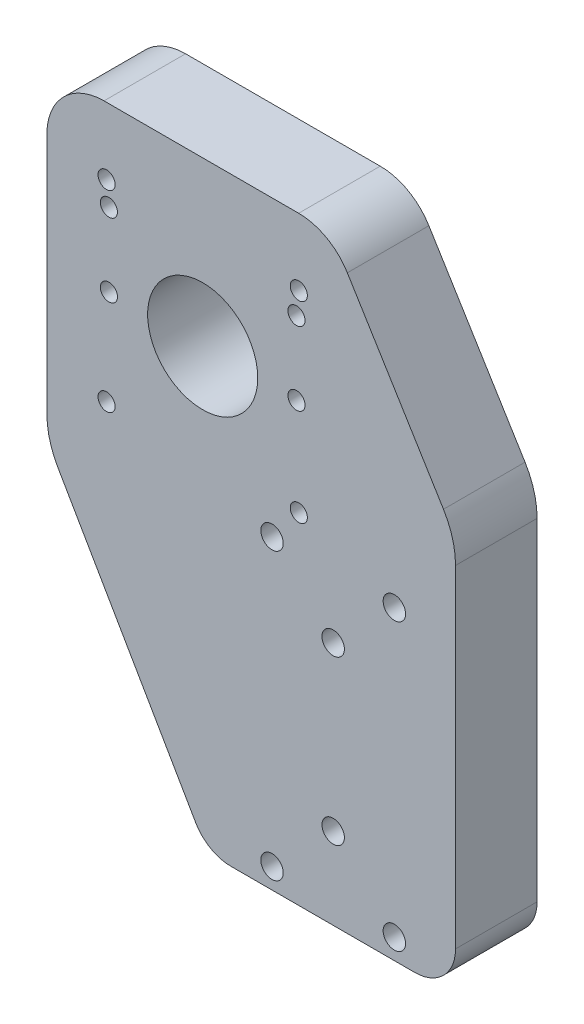
SolidWorks part; units mm, degrees
ref_plane "Front Plane" through (0, 0, 0) normal (0, 0, 1) x (1, 0, 0)
ref_plane "Top Plane" through (0, 0, 0) normal (0, 1, 0) x (1, 0, 0)
ref_plane "Right Plane" through (0, 0, 0) normal (1, 0, 0) x (0, 0, -1)
sketch "Sketch1" plane through (0, 0, 0) normal (0, 0, 1) x (1, 0, 0)
  line L0 (-130, 510) -> (13.8884, 510) construction
  line L1 (-170.2, 540.8246) -> (-129.3094, 470)
  line L2 (-116.2253, 607) -> (-90, 564.2553)
  line L15 (-90, 473) -> (-90, 564.2553)
  line L16 (-90, 473) -> (-90, 547) construction
  line L24 (-170.2, 540.8246) -> (-170.2, 607)
  line L25 (-170.2, 607) -> (-116.2253, 607)
  line L183 (-129.3094, 470) -> (-93, 470)
  arc A1 (-113.8, 602.2) -> (-116.8, 605.2) centre (-116.8, 602.2) ccw construction
  arc A13 (-90, 473) -> (-93, 470) centre (-93, 473) cw
extrude "Boss-Extrude1" add sketch "Sketch1" along normal blind 20
fillet "Fillet1" radius 10 3 edges at (-129.3094, 470, 10) (-170.2, 540.8246, 10) (-90, 564.2553, 10)
sketch "Sketch2" plane through (0, 0, 20) normal (0, 0, 1) x (1, 0, 0)
  circle A0 centre (-142, 577) radius 13.5
  dimension "D1" = 27
extrude "Cut-Extrude1" cut sketch "Sketch2" against normal blind 20
hole_wizard "Tap Drill for M5 Tap1" positions "Sketch5" profile "Sketch6" hole size "M5" standard "ISO" end condition through all
sketch "Sketch5" plane through (0, 0, 0) normal (0, 0, -1) x (-1, 0, 0)
  line L1 (119, 595) -> (119, 577)
  line L2 (119, 595) -> (165, 595)
  line L3 (165, 595) -> (165, 577)
  line L4 (119, 577) -> (165, 577)
  circle A1 centre (119, 595) radius 2.1
  point P2 (119, 595)
  point P4 (119, 577)
  point P6 (165, 577)
  point P8 (165, 595)
  dimension "D1" = 18
  dimension "D2" = 46
  dimension "D3" = 46
  dimension "D4" = 18
sketch "Sketch6" plane through (-119, 595, 0) normal (1, 0, 0) x (0, 1, 0)
  line L0 (0, 0) -> (0, 20)
  line L1 (0, 20) -> (2.1, 20)
  line L2 (2.1, 20) -> (2.1, 0)
  line L5 (2.1, 0) -> (0, 0)
  line L11 (0, -6.35) -> (0, 107.95) construction
  dimension "Thru Hole Dia." = 4.2
  dimension "Thru Hole Depth" = 20
hole_wizard "M5 Clearance Hole1" positions "Sketch7" profile "Sketch8" hole size "M5" standard "ISO" end condition through all
sketch "Sketch7" plane through (0, 0, 20) normal (0, 0, 1) x (1, 0, 0)
  point P0 (-95, 545)
  point P2 (-125, 545)
  point P4 (-125, 475)
  point P6 (-95, 475)
  point P8 (-110, 490)
  point P10 (-110, 530)
sketch "Sketch8" plane through (-95, 545, 20) normal (1, 0, 0) x (0, -1, 0)
  line L0 (0, 0) -> (0, 20)
  line L1 (0, 20) -> (2.75, 20)
  line L2 (2.75, 20) -> (2.75, 0)
  line L5 (2.75, 0) -> (0, 0)
  line L11 (0, -6.35) -> (0, 107.95) construction
  dimension "Thru Hole Dia." = 5.5
  dimension "Thru Hole Depth" = 20
hole_wizard "Tap Drill for M5 Tap2" positions "Sketch9" profile "Sketch10" hole size "M5" standard "ISO" end condition through all
sketch "Sketch9" plane through (0, 0, 20) normal (0, 0, 1) x (1, 0, 0)
  point P0 (-165.57, 553.43)
  point P2 (-165.57, 600.57)
  point P4 (-118.43, 553.43)
  point P6 (-118.43, 600.57)
sketch "Sketch10" plane through (-165.57, 553.43, 20) normal (1, 0, 0) x (0, -1, 0)
  line L0 (0, 0) -> (0, 20)
  line L1 (0, 20) -> (2.1, 20)
  line L2 (2.1, 20) -> (2.1, 0)
  line L5 (2.1, 0) -> (0, 0)
  line L11 (0, -6.35) -> (0, 107.95) construction
  dimension "Thru Hole Dia." = 4.2
  dimension "Thru Hole Depth" = 20
fillet "Fillet2" radius 4 2 edges at (-116.2253, 607, 10) (-170.2, 607, 10)
sketch "Sketch11" plane through (0, 0, 20) normal (0, 0, 1) x (1, 0, 0)
  line L0 (-82.9528, 571.8912) -> (-106.531, 610.3213)
  line L1 (-118.464, 617) -> (-166.2, 617)
  line L2 (-180.2, 603) -> (-180.2, 543.5041)
  line L3 (-177.5205, 533.5041) -> (-143.7432, 475)
  line L5 (-80, 480) -> (-80, 561.4321)
  line L6 (-91.4764, 566.6616) -> (-115.0546, 605.0918)
  line L7 (-118.464, 607) -> (-166.2, 607)
  line L8 (-170.2, 603) -> (-170.2, 543.5041)
  line L9 (-168.8603, 538.5041) -> (-132.1962, 475)
  line L10 (-123.5359, 470) -> (-93, 470)
  line L11 (-90, 473) -> (-90, 561.4321)
  line L12 (-91.4764, 566.6616) -> (-115.0546, 605.0918)
  line L13 (-118.464, 607) -> (-166.2, 607)
  line L14 (-170.2, 603) -> (-170.2, 543.5041)
  line L15 (-168.8603, 538.5041) -> (-132.1962, 475)
  line L16 (-135.0829, 470) -> (-90, 470)
  line L17 (-90, 473) -> (-90, 561.4321)
  line L18 (-123.5359, 470) -> (-93, 470) construction
  line L19 (-80, 473) -> (-80, 561.4321) construction
  line L20 (-123.5359, 460) -> (-93, 460) construction
  line L21 (-177.5205, 533.5041) -> (-140.8564, 470) construction
  arc A0 (-106.531, 610.3213) -> (-118.464, 617) centre (-118.464, 603) ccw
  arc A1 (-166.2, 617) -> (-180.2, 603) centre (-166.2, 603) ccw
  arc A2 (-180.2, 543.5041) -> (-177.5205, 533.5041) centre (-160.2, 543.5041) ccw
  arc A5 (-80, 561.4321) -> (-82.9528, 571.8912) centre (-100, 561.4321) ccw
  arc A6 (-115.0546, 605.0918) -> (-118.464, 607) centre (-118.464, 603) ccw
  arc A7 (-166.2, 607) -> (-170.2, 603) centre (-166.2, 603) ccw
  arc A8 (-170.2, 543.5041) -> (-168.8603, 538.5041) centre (-160.2, 543.5041) ccw
  arc A9 (-132.1962, 475) -> (-123.5359, 470) centre (-123.5359, 480) ccw
  arc A10 (-93, 470) -> (-90, 473) centre (-93, 473) ccw
  arc A11 (-90, 561.4321) -> (-91.4764, 566.6616) centre (-100, 561.4321) ccw
  arc A12 (-115.0546, 605.0918) -> (-118.464, 607) centre (-118.464, 603) ccw
  arc A13 (-166.2, 607) -> (-170.2, 603) centre (-166.2, 603) ccw
  arc A14 (-170.2, 543.5041) -> (-168.8603, 538.5041) centre (-160.2, 543.5041) ccw
  arc A15 (-132.1962, 475) -> (-123.5359, 470) centre (-123.5359, 480) ccw
  arc A16 (-93, 470) -> (-90, 473) centre (-93, 473) ccw
  arc A17 (-90, 561.4321) -> (-91.4764, 566.6616) centre (-100, 561.4321) ccw
  arc A18 (-93, 460) -> (-80, 473) centre (-93, 473) ccw construction
  arc A19 (-140.8564, 470) -> (-123.5359, 460) centre (-123.5359, 480) ccw construction
  arc A20 (-143.7432, 475) -> (-135.0829, 470) centre (-135.0829, 480) ccw
  arc A21 (-90, 470) -> (-80, 480) centre (-90, 480) ccw
  line M41 (-91.4764, 566.6616) -> (-115.0546, 605.0918)
  arc M42 (-115.0546, 605.0918) -> (-118.464, 607) centre (-118.464, 603) ccw
  line M43 (-118.464, 607) -> (-166.2, 607)
  arc M44 (-166.2, 607) -> (-170.2, 603) centre (-166.2, 603) ccw
  line M45 (-170.2, 603) -> (-170.2, 543.5041)
  arc M46 (-170.2, 543.5041) -> (-168.8603, 538.5041) centre (-160.2, 543.5041) ccw
  line M47 (-168.8603, 538.5041) -> (-132.1962, 475)
  arc M48 (-132.1962, 475) -> (-123.5359, 470) centre (-123.5359, 480) ccw
  arc M50 (-93, 470) -> (-90, 473) centre (-93, 473) ccw
  line M51 (-90, 473) -> (-90, 561.4321)
  arc M52 (-90, 561.4321) -> (-91.4764, 566.6616) centre (-100, 561.4321) ccw
  dimension "D3" = 10
  dimension "D1" = 0
  dimension "D2" = 10
extrude "Boss-Extrude2" add sketch "Sketch11" against normal up to surface (20 mm away) contours L16 A21 L5 A5 L0 A0 L1 A1 L2 A2 L3 A20 M48 M47 M46 M45 M44 M43 M42 M41 M52 M51 M50 region at (-82.4644, 566.3827, 20) up to face at (-163.47, 553.43, 0)
